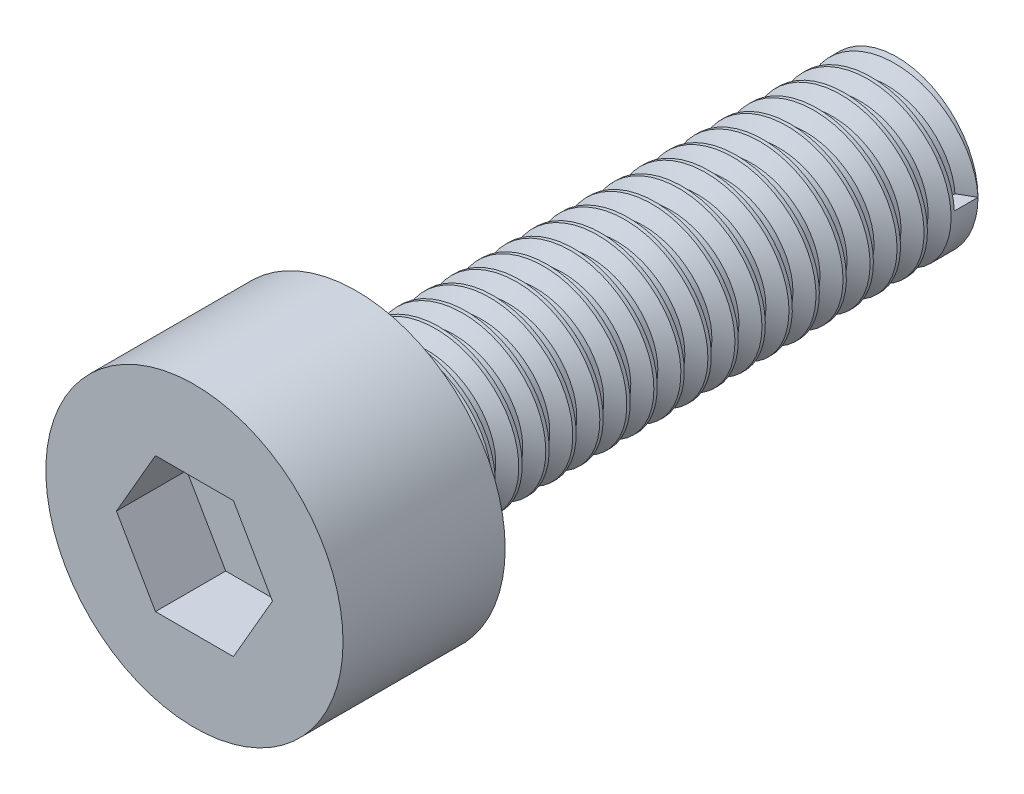
SolidWorks part; units mm, degrees
ref_plane "Front Plane" through (0, 0, 0) normal (0, 0, 1) x (1, 0, 0)
ref_plane "Top Plane" through (0, 0, 0) normal (0, 1, 0) x (1, 0, 0)
ref_plane "Right Plane" through (0, 0, 0) normal (1, 0, 0) x (0, 0, -1)
sketch "Sketch1" plane through (0, 0, 0) normal (0, 0, 1) x (1, 0, 0)
  circle A0 centre (0, 0) radius 1.5
  dimension "D1" = 3
extrude "Boss-Extrude1" add sketch "Sketch1" against normal blind 10
sketch "Sketch2" plane through (0, 0, 0) normal (0, 0, 1) x (1, 0, 0)
  circle A0 centre (0, 0) radius 2.75
  dimension "D1" = 5.5
extrude "Boss-Extrude2" add sketch "Sketch2" along normal blind 3
ref_plane "Mat_dau_vit" through (0, 0, 3) normal (0, 0, 1) x (1, 0, 0)
sketch "Sketch3" plane through (0, 0, 3) normal (0, 0, 1) x (1, 0, 0)
  line L1 (1.4434, 0) -> (0.7217, 1.25)
  line L2 (0.7217, 1.25) -> (-0.7217, 1.25)
  line L3 (-0.7217, 1.25) -> (-1.4434, 0)
  line L4 (-1.4434, 0) -> (-0.7217, -1.25)
  line L5 (-0.7217, -1.25) -> (0.7217, -1.25)
  line L6 (0.7217, -1.25) -> (1.4434, 0)
  circle A0 centre (0, 0) radius 1.25 construction
  dimension "D1" = 2.5
extrude "Cut-Extrude1" cut sketch "Sketch3" against normal blind 1.3
thread "Ren_ngoai_M3x0_5" pitch 0.5 method cut profile "Thread Profile1" start angle 0, offset 0, length 0, pitch 0.5, diameter 3
ref_plane "Plane2" through (1.5, 0, -10) normal (0, -1, 0) x (1, 0, 0)
sketch "Thread Profile1" plane through (1.5, 0, -10) normal (0, -1, 0) x (1, 0, 0)
  line L0 (0, 0) -> (0, 0.5) construction
  line L11 (0, 0) -> (0, 0.4375)
  line L12 (0, 0.4375) -> (-0.2706, 0.2812)
  line L13 (-0.2706, 0.2812) -> (-0.2706, 0.1562)
  line L15 (-0.2706, 0.1562) -> (0, 0)
  line L17 (-0.2706, 0.2187) -> (0, 0.2187) construction
  point P2 (0, 0)
  dimension "Pitch" = 0.5
  dimension "Profile_Angle" = 60
  dimension "Profile_Land" = 0.125
  dimension "Profile_Height" = 0.2706
